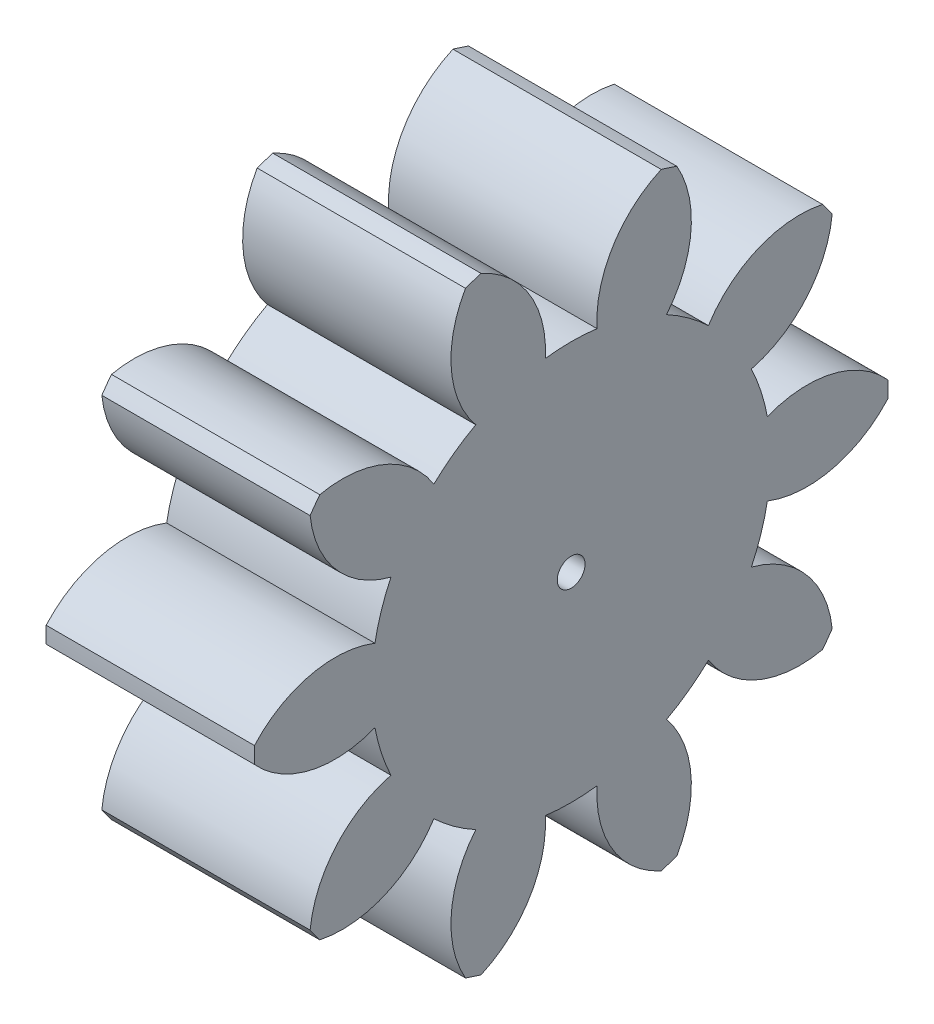
SolidWorks part; units mm, degrees
ref_plane "Plane1" through (0, 0, 0) normal (0, 0, 1) x (1, 0, 0)
ref_plane "Plane2" through (0, 0, 0) normal (0, 1, 0) x (1, 0, 0)
ref_plane "Plane3" through (0, 0, 0) normal (1, 0, 0) x (0, 0, -1)
sketch "HoldingSke" plane through (0, 0, 0) normal (0, 1, 0) x (1, 0, 0)
  line L0 (0, 0) -> (0.6565, -0.1158)
  line L1 (-15, 0) -> (100, 0) construction
  line L2 (0, 0) -> (-2.1039, 2.3779)
  line L3 (0, 0) -> (-11.863, 4.5341)
  line L4 (0, 0) -> (8.5048, 1.4996)
  line L5 (0, 0) -> (-46.8476, -17.4728)
  line L6 (0, 0) -> (-4.9738, -3.3558)
  line L7 (-2.1039, 2.3779) -> (8.6586, 51.2059)
  line L8 (-76.2, 54.61) -> (-76.1, 54.61)
  line L9 (-71.009, 38.7566) -> (-53.1078, 45.2721)
  line L10 (-76.2, 71.12) -> (104.1128, 71.12)
  line L11 (0, 0) -> (-6, 0)
  line L12 (-76.2, 101.6) -> (-76.147, 101.6)
  line L13 (24.9733, 27.94) -> (52.9518, 28.4284)
  line L14 (24.9733, 27.94) -> (24.9743, 27.94)
  line L15 (24.9733, 27.94) -> (100.4006, 29.5858)
  line L16 (-63.627, -1.5) -> (-12.827, -1.5)
  circle A0 centre (0, 0) radius 0.4
  circle A1 centre (0, 0) radius 5.624
  circle A2 centre (0, 0) radius 37.5
  circle A3 centre (0, 0) radius 0.4
  dimension "MHD" = 11.248
  dimension "Hub_dia" = 75
  dimension "Bore" = 0.8
  dimension "MBD" = 0.8
  dimension "Num_teeth" = 10
  dimension "Pitch_radius" = 180.3128
  dimension "Pitch" = 0.6667
  dimension "Width" = 6
  dimension "Overall_len" = 50
  dimension "Show_teeth" = 10
  dimension "Thickness" = 6
  dimension "OAL" = 50.0001
  dimension "T_dim" = 0.1
  dimension "Ap" = 20
  dimension "H" = 19.05
  dimension "Backlash" = 0.053
  dimension "Addendum_fac" = 1
  dimension "Dedendum_fac" = 1.25
  dimension "Clearance_fac" = 0.25
  dimension "Dedendum_add" = 0.001
  dimension "Module" = 1.5
sketch "BasProSke" plane through (0, 0, 0) normal (0, 1, 0) x (1, 0, 0)
  line L0 (-10, 0) -> (60, 0) construction
  line L1 (0, 0) -> (0, 9)
  line L2 (0, 0) -> (6, 0)
  line L3 (6, 0) -> (6, 9)
  line L4 (6, 9) -> (0, 9)
  dimension "Diameter" = 18
  dimension "Thickness" = 6
revolve "Base-Revolve" add sketch "BasProSke" angle 360 about L0
sketch "TooCutSke" plane through (0, 0, 0) normal (1, 0, 0) x (0, 0, -1)
  line L1 (0, 0) -> (0, 107) construction
  line L2 (0, 0) -> (-1.2658, 7.3924) construction
  line L3 (0, 0) -> (-4.5869, 14.117) construction
  line L4 (-1.2658, 7.3924) -> (-2.2934, 7.0585) construction
  arc A0 (0.8839, 5.5541) -> (-0.8839, 5.5541) centre (0, 0) ccw
  arc A1 (2.6378, 8.6313) -> (-2.6378, 8.6313) centre (0, 0) ccw
  circle A2 centre (0, 0) radius 7.5 construction
  circle A3 centre (0, 0) radius 7.0477 construction
  arc A4 (-0.8839, 5.5541) -> (-2.6378, 8.6313) centre (-3.8646, 5.8936) ccw
  arc A5 (2.6378, 8.6313) -> (0.8839, 5.5541) centre (3.8646, 5.8936) ccw
  dimension "Root_dia" = 11.248
  dimension "Overcut_dia" = 18.0508
  dimension "Pitch_dia" = 15
  dimension "Base_dia" = 14.0954
  dimension "Flank_rad" = 3
  dimension "Half_ang" = 18
  dimension "Half_CT" = 1.0805
extrude "ToothCut" cut sketch "TooCutSke" along normal through all
fillet "Breaks" [suppressed] radius 0.03 tangent propagation no
fillet "RootFillets" [suppressed] radius 0.376
pattern_circular "TeethCuts" count 10 every 36 about axis through (-10, 0, 0) along (1, 0, 0) of "ToothCut", "RootFillets", "Breaks"
sketch "HubNeaOneSke" plane through (0, 0, 0) normal (-1, 0, 0) x (0, 0, 1)
  circle A0 centre (0, 0) radius 5.624
  dimension "Diameter" = 11.248
extrude "HubNearOne" [suppressed] add sketch "HubNeaOneSke" along normal blind 44.0001
sketch "HubNeaBotSke" plane through (0, 0, 0) normal (-1, 0, 0) x (0, 0, 1)
  circle A0 centre (0, 0) radius 5.624
  dimension "Diameter" = 11.248
extrude "HubNearBoth" [suppressed] add sketch "HubNeaBotSke" along normal blind 22
ref_plane "FarPln" through (6, 0, 0) normal (1, 0, 0) x (0, 0, -1)
sketch "HubFarSke" plane through (6, 0, 0) normal (1, 0, 0) x (0, 0, -1)
  circle A0 centre (0, 0) radius 5.624
  dimension "Diameter" = 11.248
extrude "HubFar" [suppressed] add sketch "HubFarSke" along normal blind 22
sketch "BorSke" plane through (0, 0, 0) normal (1, 0, 0) x (0, 0, -1)
  circle A0 centre (0, 0) radius 0.4
  dimension "Diameter" = 0.8
extrude "Bore" cut sketch "BorSke" along normal mid plane 100.0001
sketch "KeySke" plane through (0, 0, 0) normal (1, 0, 0) x (0, 0, -1)
  line L0 (-0.05, 0) -> (-0.05, 0.5)
  line L1 (-0.05, 0.5) -> (0.05, 0.5)
  line L2 (0.05, 0.5) -> (0.05, 0)
  line L3 (0, 0) -> (0, 34) construction
  line L4 (-0.05, 0) -> (0.05, 0)
  dimension "Offset" = 0.5
  dimension "Width" = 0.1
extrude "Keyway" [suppressed] cut sketch "KeySke" along normal mid plane 100.0001
pattern_circular "Keyway2" [suppressed] count 2 every 90 about axis through (-10, 0, 0) along (1, 0, 0)
sketch "Sketch2" plane through (6, 0, 0) normal (1, 0, 0) x (0, 0, -1)
  circle A40 centre (0, 0) radius 0.4
  circle A41 centre (0, 0) radius 0.4 construction
  arc A80 (7.2407, 5.5531) -> (3.9538, 4.1735) centre (6.5907, 2.4965) ccw
  arc A81 (3.9538, 4.1735) -> (2.7475, 5.05) centre (0, 0) ccw
  arc A82 (2.7475, 5.05) -> (3.0438, 8.6024) centre (0.3377, 7.0396) ccw
  arc A83 (3.0438, 8.6024) -> (2.5938, 8.7486) centre (0, 0) ccw
  arc A84 (2.5938, 8.7486) -> (0.7456, 5.7004) centre (3.8646, 5.8936) ccw
  arc A85 (0.7456, 5.7004) -> (-0.7456, 5.7004) centre (0, 0) ccw
  arc A86 (-0.7456, 5.7004) -> (-2.5938, 8.7486) centre (-3.8646, 5.8936) ccw
  arc A87 (-2.5938, 8.7486) -> (-3.0438, 8.6024) centre (0, 0) ccw
  arc A88 (-3.0438, 8.6024) -> (-2.7475, 5.05) centre (-0.3377, 7.0396) ccw
  arc A89 (-2.7475, 5.05) -> (-3.9538, 4.1735) centre (0, 0) ccw
  arc A90 (-3.9538, 4.1735) -> (-7.2407, 5.5531) centre (-6.5907, 2.4965) ccw
  arc A91 (-7.2407, 5.5531) -> (-7.5189, 5.1703) centre (0, 0) ccw
  arc A92 (-7.5189, 5.1703) -> (-5.1911, 2.4706) centre (-4.4109, 5.4967) ccw
  arc A93 (-5.1911, 2.4706) -> (-5.6518, 1.0524) centre (0, 0) ccw
  arc A94 (-5.6518, 1.0524) -> (-9.1219, 0.2366) centre (-6.7994, -1.8542) ccw
  arc A95 (-9.1219, 0.2366) -> (-9.1219, -0.2366) centre (0, 0) ccw
  arc A96 (-9.1219, -0.2366) -> (-5.6518, -1.0524) centre (-6.7994, 1.8542) ccw
  arc A97 (-5.6518, -1.0524) -> (-5.1911, -2.4706) centre (0, 0) ccw
  arc A98 (-5.1911, -2.4706) -> (-7.5189, -5.1703) centre (-4.4109, -5.4967) ccw
  arc A99 (-7.5189, -5.1703) -> (-7.2407, -5.5531) centre (0, 0) ccw
  arc A100 (-7.2407, -5.5531) -> (-3.9538, -4.1735) centre (-6.5907, -2.4965) ccw
  arc A101 (-3.9538, -4.1735) -> (-2.7475, -5.05) centre (0, 0) ccw
  arc A102 (-2.7475, -5.05) -> (-3.0438, -8.6024) centre (-0.3377, -7.0396) ccw
  arc A103 (-3.0438, -8.6024) -> (-2.5938, -8.7486) centre (0, 0) ccw
  arc A104 (-2.5938, -8.7486) -> (-0.7456, -5.7004) centre (-3.8646, -5.8936) ccw
  arc A105 (-0.7456, -5.7004) -> (0.7456, -5.7004) centre (0, 0) ccw
  arc A106 (0.7456, -5.7004) -> (2.5938, -8.7486) centre (3.8646, -5.8936) ccw
  arc A107 (2.5938, -8.7486) -> (3.0438, -8.6024) centre (0, 0) ccw
  arc A108 (3.0438, -8.6024) -> (2.7475, -5.05) centre (0.3377, -7.0396) ccw
  arc A109 (2.7475, -5.05) -> (3.9538, -4.1735) centre (0, 0) ccw
  arc A110 (3.9538, -4.1735) -> (7.2407, -5.5531) centre (6.5907, -2.4965) ccw
  arc A111 (7.2407, -5.5531) -> (7.5189, -5.1703) centre (0, 0) ccw
  arc A112 (7.5189, -5.1703) -> (5.1911, -2.4706) centre (4.4109, -5.4967) ccw
  arc A113 (5.1911, -2.4706) -> (5.6518, -1.0524) centre (0, 0) ccw
  arc A114 (5.6518, -1.0524) -> (9.1219, -0.2366) centre (6.7994, 1.8542) ccw
  arc A115 (9.1219, -0.2366) -> (9.1219, 0.2366) centre (0, 0) ccw
  arc A116 (9.1219, 0.2366) -> (5.6518, 1.0524) centre (6.7994, -1.8542) ccw
  arc A117 (5.6518, 1.0524) -> (5.1911, 2.4706) centre (0, 0) ccw
  arc A118 (5.1911, 2.4706) -> (7.5189, 5.1703) centre (4.4109, 5.4967) ccw
  arc A119 (7.5189, 5.1703) -> (7.2407, 5.5531) centre (0, 0) ccw
  arc A120 (7.2407, 5.5531) -> (3.9538, 4.1735) centre (6.5907, 2.4965) ccw
  arc A121 (3.9538, 4.1735) -> (2.7475, 5.05) centre (0, 0) ccw
  arc A122 (2.7475, 5.05) -> (3.0438, 8.6024) centre (0.3377, 7.0396) ccw
  arc A123 (3.0438, 8.6024) -> (2.5938, 8.7486) centre (0, 0) ccw
  arc A124 (2.5938, 8.7486) -> (0.7456, 5.7004) centre (3.8646, 5.8936) ccw
  arc A125 (0.7456, 5.7004) -> (-0.7456, 5.7004) centre (0, 0) ccw
  arc A126 (-0.7456, 5.7004) -> (-2.5938, 8.7486) centre (-3.8646, 5.8936) ccw
  arc A127 (-2.5938, 8.7486) -> (-3.0438, 8.6024) centre (0, 0) ccw
  arc A128 (-3.0438, 8.6024) -> (-2.7475, 5.05) centre (-0.3377, 7.0396) ccw
  arc A129 (-2.7475, 5.05) -> (-3.9538, 4.1735) centre (0, 0) ccw
  arc A130 (-3.9538, 4.1735) -> (-7.2407, 5.5531) centre (-6.5907, 2.4965) ccw
  arc A131 (-7.2407, 5.5531) -> (-7.5189, 5.1703) centre (0, 0) ccw
  arc A132 (-7.5189, 5.1703) -> (-5.1911, 2.4706) centre (-4.4109, 5.4967) ccw
  arc A133 (-5.1911, 2.4706) -> (-5.6518, 1.0524) centre (0, 0) ccw
  arc A134 (-5.6518, 1.0524) -> (-9.1219, 0.2366) centre (-6.7994, -1.8542) ccw
  arc A135 (-9.1219, 0.2366) -> (-9.1219, -0.2366) centre (0, 0) ccw
  arc A136 (-9.1219, -0.2366) -> (-5.6518, -1.0524) centre (-6.7994, 1.8542) ccw
  arc A137 (-5.6518, -1.0524) -> (-5.1911, -2.4706) centre (0, 0) ccw
  arc A138 (-5.1911, -2.4706) -> (-7.5189, -5.1703) centre (-4.4109, -5.4967) ccw
  arc A139 (-7.5189, -5.1703) -> (-7.2407, -5.5531) centre (0, 0) ccw
  arc A140 (-7.2407, -5.5531) -> (-3.9538, -4.1735) centre (-6.5907, -2.4965) ccw
  arc A141 (-3.9538, -4.1735) -> (-2.7475, -5.05) centre (0, 0) ccw
  arc A142 (-2.7475, -5.05) -> (-3.0438, -8.6024) centre (-0.3377, -7.0396) ccw
  arc A143 (-3.0438, -8.6024) -> (-2.5938, -8.7486) centre (0, 0) ccw
  arc A144 (-2.5938, -8.7486) -> (-0.7456, -5.7004) centre (-3.8646, -5.8936) ccw
  arc A145 (-0.7456, -5.7004) -> (0.7456, -5.7004) centre (0, 0) ccw
  arc A146 (0.7456, -5.7004) -> (2.5938, -8.7486) centre (3.8646, -5.8936) ccw
  arc A147 (2.5938, -8.7486) -> (3.0438, -8.6024) centre (0, 0) ccw
  arc A148 (3.0438, -8.6024) -> (2.7475, -5.05) centre (0.3377, -7.0396) ccw
  arc A149 (2.7475, -5.05) -> (3.9538, -4.1735) centre (0, 0) ccw
  arc A150 (3.9538, -4.1735) -> (7.2407, -5.5531) centre (6.5907, -2.4965) ccw
  arc A151 (7.2407, -5.5531) -> (7.5189, -5.1703) centre (0, 0) ccw
  arc A152 (7.5189, -5.1703) -> (5.1911, -2.4706) centre (4.4109, -5.4967) ccw
  arc A153 (5.1911, -2.4706) -> (5.6518, -1.0524) centre (0, 0) ccw
  arc A154 (5.6518, -1.0524) -> (9.1219, -0.2366) centre (6.7994, 1.8542) ccw
  arc A155 (9.1219, -0.2366) -> (9.1219, 0.2366) centre (0, 0) ccw
  arc A156 (9.1219, 0.2366) -> (5.6518, 1.0524) centre (6.7994, -1.8542) ccw
  arc A157 (5.6518, 1.0524) -> (5.1911, 2.4706) centre (0, 0) ccw
  arc A158 (5.1911, 2.4706) -> (7.5189, 5.1703) centre (4.4109, 5.4967) ccw
  arc A159 (7.5189, 5.1703) -> (7.2407, 5.5531) centre (0, 0) ccw
  dimension "D1" = 0.125
extrude "Boss-Extrude2" add sketch "Sketch2" against normal up to surface (6 mm away) up to face at (0, 0, 0)
equation "' \"Module@HoldingSke\" = 6.35"
equation "' \"Num_teeth@HoldingSke\" = 12"
equation "' \"Ap@HoldingSke\" =  20"
equation "' \"Width@HoldingSke\" = 0.5 * 25.4"
equation "' \"Hub_dia@HoldingSke\"= 1 * 25.4"
equation "' \"Overall_len@HoldingSke\" = 1.0 * 25.4"
equation "' \"Bore@HoldingSke\" = 0.75 * 25.4"
equation "' \"T_dim@HoldingSke\" = 0.1 * 25.4"
equation "' \"Width@KeySke\" = 0.25 * 25.4"
equation "' \"Show_teeth@HoldingSke\" = 13"
equation "' \"Backlash@HoldingSke\" = 0.009 * 25.4"
equation "' \"Addendum_fac@HoldingSke\" = 1.0"
equation "' \"Dedendum_fac@HoldingSke\" = 1.25"
equation "' \"Dedendum_add@HoldingSke\" = 0.00005 * 25.4"
equation "' \"Clearance_fac@HoldingSke\" = 0.25"
equation "\"Pitch@HoldingSke\" = 1 / \"Module@HoldingSke\""
equation "\"Overcut_dia@TooCutSke\" = (\"Num_teeth@HoldingSke\" + 2 * \"Addendum_fac@HoldingSke\") / \"Pitch@HoldingSke\" + 0.002 * 25.4"
equation "\"Pitch_dia@TooCutSke\" = \"Num_teeth@HoldingSke\" / \"Pitch@HoldingSke\""
equation "\"Base_dia@TooCutSke\" = \"Num_teeth@HoldingSke\" / \"Pitch@HoldingSke\" * cos((\"Ap@HoldingSke\"  * 3.14159265 / 180))"
equation "\"Root_dia@TooCutSke\" = (\"Num_teeth@HoldingSke\" + 2) / \"Pitch@HoldingSke\" - 2 * (\"Addendum_fac@HoldingSke\" + \"Dedendum_fac@HoldingSke\") / \"Pitch@HoldingSke\" - \"Dedendum_add@HoldingSke\" * 2"
equation "\"Half_ang@TooCutSke\" = 180 / \"Num_teeth@HoldingSke\""
equation "\"Half_CT@TooCutSke\" = \"Num_teeth@HoldingSke\" / \"Pitch@HoldingSke\" * sin((3.14159265 / 2 / \"Num_teeth@HoldingSke\")) / 2 - 7 * \"Backlash@HoldingSke\" / 4"
equation "\"Flank_rad@TooCutSke\" = \"Num_teeth@HoldingSke\" / \"Pitch@HoldingSke\" / 5"
equation "\"Radius@RootFillets\" = \"Clearance_fac@HoldingSke\" / \"Pitch@HoldingSke\" + \"Dedendum_add@HoldingSke\""
equation "\"Break_rad@Breaks\" = 0.02 / \"Pitch@HoldingSke\""
equation "\"Thickness@HoldingSke\" = \"Width@HoldingSke\""
equation "\"OAL@HoldingSke\" = \"Thickness@HoldingSke\""
equation "\"MHD@HoldingSke\" = (\"Num_teeth@HoldingSke\" + 2) / \"Pitch@HoldingSke\" - 2 * (\"Addendum_fac@HoldingSke\" + \"Dedendum_fac@HoldingSke\")  / \"Pitch@HoldingSke\" - \"Dedendum_add@HoldingSke\" * 2"
equation "\"MBD@HoldingSke\" = (\"Num_teeth@HoldingSke\" + 2) / \"Pitch@HoldingSke\" - 2 * (\"Addendum_fac@HoldingSke\" + \"Dedendum_fac@HoldingSke\")  / \"Pitch@HoldingSke\" - \"Dedendum_add@HoldingSke\" * 2 - 0.002 * 25.4"
equation "\"MHD@HoldingSke\" = ((sgn( \"MHD@HoldingSke\" - \"Hub_dia@HoldingSke\" )-1)*( \"MHD@HoldingSke\" - \"Hub_dia@HoldingSke\" ))/-2+ \"Hub_dia@HoldingSke\""
equation "\"MBD@HoldingSke\" = ((sgn( \"MBD@HoldingSke\" - \"Bore@HoldingSke\" )-1)*( \"MBD@HoldingSke\" - \"Bore@HoldingSke\" ))/-2+ \"Bore@HoldingSke\""
equation "\"OAL@HoldingSke\" = ((sgn( \"OAL@HoldingSke\" - \"Overall_len@HoldingSke\" )+1)*( \"OAL@HoldingSke\" - \"Overall_len@HoldingSke\" ))/2 + \"Overall_len@HoldingSke\" + 0.000002 * 25.4"
equation "\"Num_teeth@TeethCuts\" = int( \"Show_teeth@HoldingSke\" ) + 1"
equation "\"Num_teeth@TeethCuts\" = ((sgn( \"Num_teeth@TeethCuts\" - \"Num_teeth@HoldingSke\" )-1)*( \"Num_teeth@TeethCuts\" - \"Num_teeth@HoldingSke\" ))/-2+ \"Num_teeth@HoldingSke\""
equation "\"Num_teeth@TeethCuts\" = ((sgn( \"Num_teeth@TeethCuts\" - 2.0)+1)*( \"Num_teeth@TeethCuts\" - 2.0))/2 +2.0"
equation "\"Angle@TeethCuts\" = 360.0 / \"Num_teeth@HoldingSke\""
equation "\"Diameter@BasProSke\" = (\"Num_teeth@HoldingSke\" + 2 * \"Addendum_fac@HoldingSke\") / \"Pitch@HoldingSke\""
equation "\"Thickness@BasProSke\"  = \"Thickness@HoldingSke\""
equation "' \"Fillet_rad@BasProSke\" =  \"Thickness@HoldingSke\" * 0.05"
equation "\"MHD@HoldingSke\" = ((sgn( \"MHD@HoldingSke\" - \"Root_dia@TooCutSke\" )-1)*( \"MHD@HoldingSke\" - \"Root_dia@TooCutSke\" ))/-2+ \"Root_dia@TooCutSke\""
equation "\"Diameter@HubNeaOneSke\" = \"MHD@HoldingSke\""
equation "\"Length@HubNearOne\" = \"OAL@HoldingSke\" - \"Thickness@BasProSke\""
equation "\"Diameter@HubNeaBotSke\" = \"MHD@HoldingSke\""
equation "\"Length@HubNearBoth\" = ( \"OAL@HoldingSke\" - \"Thickness@BasProSke\" ) / 2.0"
equation "\"Thickness@FarPln\" = \"Thickness@BasProSke\""
equation "\"Diameter@HubFarSke\" = \"MHD@HoldingSke\""
equation "\"Length@HubFar\" = ( \"OAL@HoldingSke\" - \"Thickness@BasProSke\" ) / 2.0"
equation "\"Diameter@BorSke\" = \"MBD@HoldingSke\""
equation "\"D1@Bore\" = \"OAL@HoldingSke\" * 2.0"
equation "\"D1@Keyway\" = \"OAL@HoldingSke\" * 2.0"
equation "\"Offset@KeySke\" = \"T_dim@HoldingSke\" + \"MBD@HoldingSke\" / 2.0"
